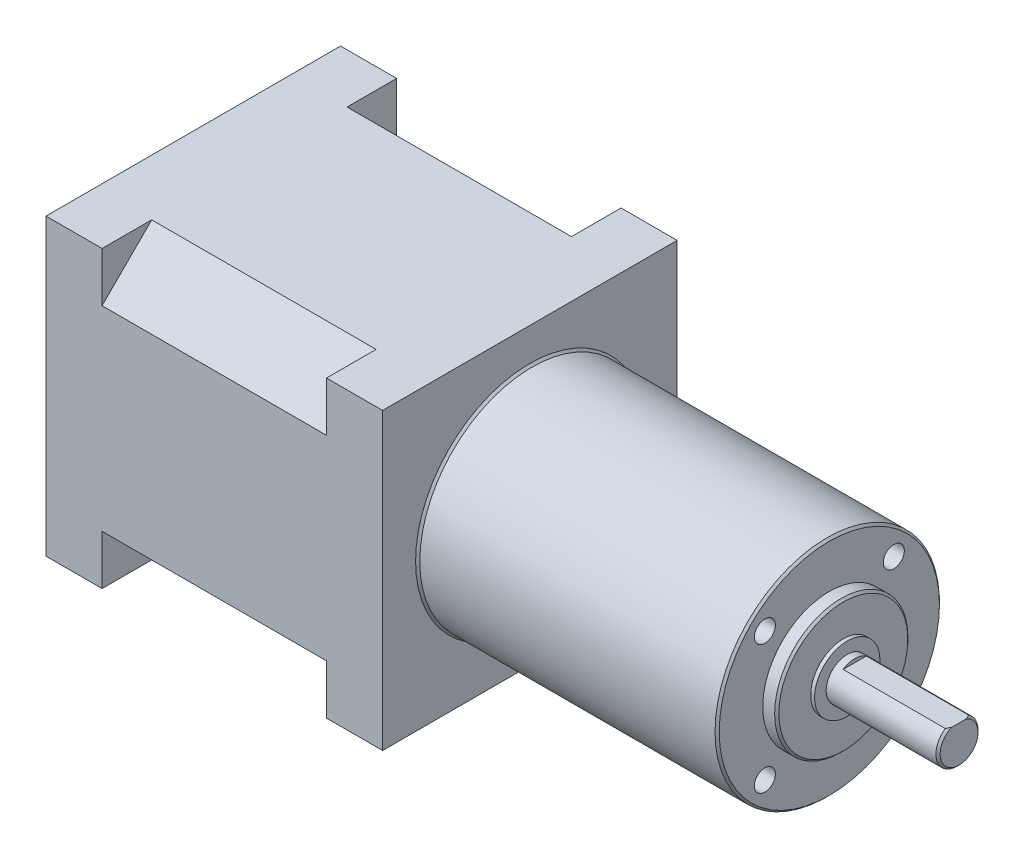
SolidWorks part; units mm, degrees
ref_plane "Front Plane" through (0, 0, 0) normal (0, 0, 1) x (1, 0, 0)
ref_plane "Top Plane" through (0, 0, 0) normal (0, 1, 0) x (1, 0, 0)
ref_plane "Right Plane" through (0, 0, 0) normal (1, 0, 0) x (0, 0, -1)
sketch "Sketch1" plane through (0, 0, 0) normal (1, 0, 0) x (0, 0, -1)
  line L1 (0, 0) -> (42, 0)
  line L2 (0, 0) -> (0, 42)
  line L3 (0, 42) -> (42, 42)
  line L4 (42, 0) -> (42, 42)
  dimension "D1" = 42
  dimension "D2" = 42
extrude "Boss-Extrude1" add sketch "Sketch1" along normal blind 48
sketch "Sketch2" plane through (48, 0, 0) normal (1, 0, 0) x (0, 0, -1)
  line L0 (42, 42) -> (0, 0) construction
  line L1 (0, 0) -> (0, 42) construction
  line L3 (42, 0) -> (0, 42) construction
  circle A0 centre (21, 21) radius 16
  dimension "D1" = 32
extrude "Boss-Extrude2" add sketch "Sketch2" along normal blind 42.7
ref_plane "Plane1" through (0, 0, -21) normal (0, 0, -1) x (-1, 0, 0)
ref_axis "Axis1" through (90.7, 3.4, -21) along (0, 1, 0)
sketch "Sketch5" plane through (0, 0, -21) normal (0, 0, -1) x (-1, 0, 0)
  line L0 (-90.7, 30.5) -> (-92.7, 30.5)
  line L1 (-90.7, 3.4) -> (-90.7, 38.6) construction
  line L2 (-92.7, 30.5) -> (-92.7, 25.6561)
  line L3 (-92.7, 25.6561) -> (-93.2522, 25.6561)
  line L4 (-93.2522, 25.6561) -> (-93.2522, 24)
  line L5 (-93.2522, 24) -> (-109.2, 24)
  line L6 (-90.7, 5) -> (-90.7, 37) construction
  line L7 (-90.7, 37) -> (-90.7, 21) construction
  line L8 (-90.7, 21) -> (-134.976, 21) construction
  line L9 (-109.2, 24) -> (-109.2, 21)
  line L10 (-109.2, 21) -> (-90.7, 21)
  line L11 (-90.7, 21) -> (-90.7, 30.5)
  dimension "D1" = 2
  dimension "D2" = 9.5
  dimension "D3" = 3
  dimension "D4" = 18.5
revolve "Revolve1" add sketch "Sketch5" angle 360 about L10
ref_plane "Plane2" through (0, 21, 0) normal (0, 1, 0) x (1, 0, 0)
ref_plane "Plane3" through (0, 23.5, 0) normal (0, 1, 0) x (1, 0, 0)
sketch "Sketch7" plane through (0, 23.5, 0) normal (0, 1, 0) x (1, 0, 0)
  line L1 (110.9023, 14.5732) -> (94.3149, 14.5732)
  line L2 (110.9023, 14.5732) -> (110.9023, 26.4817)
  line L3 (110.9023, 26.4817) -> (94.3149, 26.4817)
  line L4 (94.3149, 14.5732) -> (94.3149, 26.4817)
extrude "Cut-Extrude1" cut sketch "Sketch7" along normal blind 2
chamfer "Chamfer1" distance 0.3 angle 45 4 edges at (48, 21, -5) (90.7, 21, -37) (92.7, 21, -30.5) (109.2, 18, -21)
sketch "Sketch8" plane through (90.7, 0, 0) normal (1, 0, 0) x (0, 0, -1)
  circle A0 centre (21, 21) radius 13
  circle A1 centre (21, 34) radius 1.5
  circle A2 centre (30.1924, 30.1924) radius 1.5
  circle A3 centre (34, 21) radius 1.5
  circle A4 centre (30.1924, 11.8076) radius 1.5
  circle A5 centre (21, 8) radius 1.5
  circle A6 centre (11.8076, 11.8076) radius 1.5
  circle A7 centre (8, 21) radius 1.5
  circle A8 centre (11.8076, 30.1924) radius 1.5
  point P21 (21, 21)
  dimension "D1" = 26
  dimension "D2" = 3
  dimension "D3" = 8
extrude "Cut-Extrude2" cut sketch "Sketch8" against normal blind 10 contours A0 A2 | A0 A2 | A0 A4 | A0 A4 | A0 A6 | A0 A6 | A0 A8 | A0 A8 region at (90.7, 29.7314, -29.7314) region at (90.7, 30.6313, -30.6313) region at (90.7, 11.3687, -30.6313) region at (90.7, 12.2686, -29.7314) region at (90.7, 29.7314, -12.2686) region at (90.7, 30.6313, -11.3687) region at (90.7, 11.3687, -11.3687) region at (90.7, 12.2686, -12.2686)
ref_plane "Plane4" through (40, 0, 0) normal (1, 0, 0) x (0, 0, -1)
sketch "Sketch9" plane through (40, 0, 0) normal (1, 0, 0) x (0, 0, -1)
  line L0 (42, 34.9289) -> (34.9289, 42)
  line L1 (42, 42) -> (0, 42)
  line L2 (42, 42) -> (42, 0)
  line L3 (42, 0) -> (0, 0)
  line L4 (0, 42) -> (0, 0)
  line L5 (34.9289, 42) -> (7.0711, 42)
  line L6 (7.0711, 42) -> (0, 34.9289)
  line L7 (0, 34.9289) -> (0, 7.0711)
  line L8 (0, 7.0711) -> (7.0711, 0)
  line L9 (7.0711, 0) -> (34.9289, 0)
  line L10 (34.9289, 0) -> (42, 7.0711)
  line L11 (42, 7.0711) -> (42, 34.9289)
  dimension "D1" = 45
  dimension "D2" = 45
  dimension "D3" = 10
  dimension "D4" = 10
  dimension "D5" = 10
extrude "Cut-Extrude3" cut sketch "Sketch9" against normal blind 32 contours L6 L1 L4 | L8 L4 L3 | L10 L3 L2 | L2 L1 L0 region at (40, 39.643, -39.643) region at (40, 2.357, -39.643) region at (40, 39.643, -2.357) region at (40, 2.357, -2.357)
